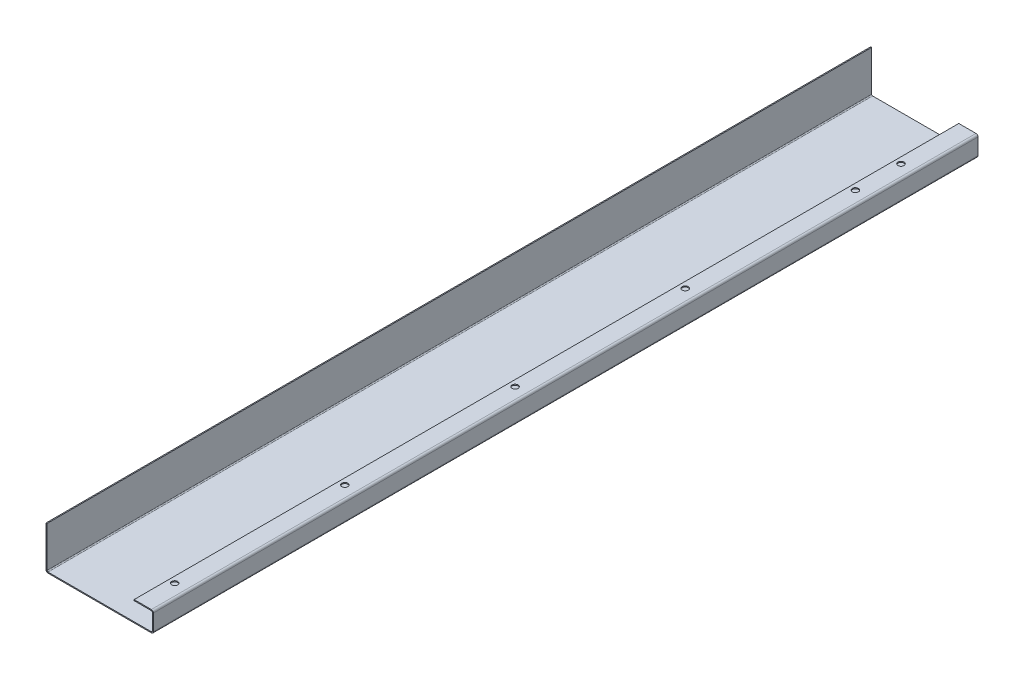
SolidWorks part; units mm, degrees
note: The reader was unsure of these and kept them because the rebuilt part matched: flange length of "Edge-Flange1", "Edge-Flange2", "Edge-Flange4".
ref_plane "Front Plane" through (0, 0, 0) normal (0, 0, 1) x (1, 0, 0)
ref_plane "Top Plane" through (0, 0, 0) normal (0, 1, 0) x (1, 0, 0)
ref_plane "Right Plane" through (0, 0, 0) normal (1, 0, 0) x (0, 0, -1)
sketch "Sketch1" plane through (0, 0, 0) normal (0, 1, 0) x (1, 0, 0)
  line L1 (0, 0) -> (106, 0)
  line L2 (0, 0) -> (0, 814)
  line L3 (0, 814) -> (106, 814)
  line L4 (106, 0) -> (106, 814)
  dimension "D1" = 106
  dimension "D2" = 814
base flange "Base-Flange1" sketch "Sketch1" thickness 1 reverse thickness direction no parameters "D1"=1
edge flange "Edge-Flange1" sketch "Sketch8" flange angle 90 flange length 19 flange position material inside bend radius 1 thickness 1 relief rectangular parameters "D6"=10
sketch "Sketch8" plane through (106, 0, 0) normal (1, 0, 0) x (0, 0, -1)
  line L0 (0, 0) -> (814, 0) construction
  line L1 (0, 0) -> (814, 0)
  line L2 (0, 0) -> (0, 19)
  line L3 (0, 19) -> (814, 19)
  line L4 (814, 19) -> (814, 0)
bend "EdgeBend1" bend radius 1 bend angle 90 parameters "D5"=1
edge flange "Edge-Flange2" sketch "Sketch11" flange angle 90 flange length 18 flange position material inside bend radius 1 thickness 1 relief rectangular parameters "D6"=10
sketch "Sketch11" plane through (105, 19, 0) normal (0, 1, 0) x (0, 0, -1)
  line L0 (814, 0) -> (0, 0) construction
  line L1 (814, 0) -> (0, 0)
  line L2 (0, 0) -> (0, 18)
  line L3 (0, 18) -> (814, 18)
  line L4 (814, 18) -> (814, 0)
bend "EdgeBend2" bend radius 1 bend angle 90 parameters "D5"=2
sketch "Sketch12" plane through (0, -1, 0) normal (0, -1, 0) x (-1, 0, 0)
  line L0 (0, 814) -> (-106, 752.8009)
  line L1 (-106, 814) -> (-106, 0) construction
  line L2 (-106, 752.8009) -> (-106, 814)
  line L3 (-106, 814) -> (0, 814)
  dimension "D1" = 30
extrude "Cut-Extrude1" [suppressed] cut sketch "Sketch12" against normal through all
edge flange "Edge-Flange3" [suppressed] sketch "Sketch15" flange angle 90 flange position material outside bend radius 1 thickness 1
sketch "Sketch15" plane through (433.0127, 0, -750) normal (0.5, 0, -0.866) x (-0.866, 0, -0.5)
  line L0 (414.5522, 0) -> (500, 0) construction
  line L1 (414.5522, 0) -> (500, 0)
  line L2 (414.5522, 0) -> (414.5522, 17.1875)
  line L3 (428.0522, 18.9875) -> (500, 18.9875)
  line L4 (500, 18.9875) -> (500, 0)
  line L5 (428.0522, 18.9875) -> (428.0522, 17.1875)
  line L6 (428.0522, 17.1875) -> (414.5522, 17.1875)
  dimension "D1" = 1.8
  dimension "D2" = 13.5
bend "EdgeBend3" bend radius 1 bend angle 90 parameters "D5"=3, "D6"=10, "D7"=18.9875
edge flange "Edge-Flange4" sketch "Sketch18" flange angle 90 flange length 41 flange position material inside bend radius 1 thickness 1 relief rectangular parameters "D6"=10
sketch "Sketch18" plane through (0, 0, 0) normal (-1, 0, 0) x (0, 0, 1)
  line L0 (-814, 0) -> (0, 0) construction
  line L1 (-814, 0) -> (0, 0)
  line L2 (-814, 0) -> (-814, 41)
  line L3 (-814, 41) -> (0, 41)
  line L4 (0, 41) -> (0, 0)
bend "EdgeBend4" bend radius 1 bend angle 90 parameters "D5"=3
sketch "Sketch19" plane through (0, 19, 0) normal (0, 1, 0) x (1, 0, 0)
  line L0 (104, 814) -> (87, 814) construction
  line L1 (87, 814) -> (87, 0) construction
  circle A0 centre (93, 751) radius 3
  circle A7 centre (93, 706) radius 3
  circle A8 centre (93, 538) radius 3
  circle A9 centre (93, 370) radius 3
  circle A10 centre (93, 202) radius 3
  circle A11 centre (93, 34) radius 3
  dimension "D1" = 6
  dimension "D3" = 6
  dimension "D5" = 5
  dimension "D4" = 45
  dimension "D2" = 63
extrude "Cut-Extrude2" cut sketch "Sketch19" against normal blind 10 normal cut yes
sketch "Bend-Lines1" [suppressed] plane through (0, 0, 0) normal (0, 1, 0) x (1, 0, 0)
sketch "Bounding-Box1" [suppressed] plane through (0, 0, 0) normal (0, 1, 0) x (1, 0, 0)
sheet metal parameters "Sheet-Metal1" thickness 1 parameters "D1"=1
flat pattern "Flat-Pattern1" [suppressed]
sketch "Bend-Lines2" plane through (0, 0, 0) normal (0, 1, 0) x (1, 0, 0)
sketch3d "Bounding-Box2" [suppressed]
  line L0 (0, 0, 0) -> (0, 1577, 0) construction
  line L1 (-76, 0, 0) -> (-76, 1577, 0) construction
  line L2 (0, 0, 0) -> (-76, 0, 0) construction
  line L3 (0, 1577, 0) -> (-76, 1577, 0) construction
sheet metal parameters "Sheet-Metal2" thickness 1 parameters "D1"=1
flat pattern "Flat-Pattern1"
sketch "Bend-Lines2" plane through (0, 0, 0) normal (0, 1, 0) x (1, 0, 0)
  line L0 (75.1781, 0) -> (75.1781, 1577) construction
  line L1 (75.1781, 0) -> (75.1781, 1577) construction
sketch3d "Bounding-Box2" [suppressed]
  line L0 (0, 0, 0) -> (0, 1577, 0) construction
  line L1 (95.3562, 0, 0) -> (95.3562, 1577, 0) construction
  line L2 (0, 0, 0) -> (95.3562, 0, 0) construction
  line L3 (0, 1577, 0) -> (95.3562, 1577, 0) construction
bend of the flat pattern "Flatten-<EdgeBend1>1"
sheet metal parameters "Sheet-Metal3" thickness 1 parameters "D1"=1
flat pattern "Flat-Pattern1"
sketch "Bend-Lines2" plane through (0, 0, 0) normal (0, 1, 0) x (1, 0, 0)
  line L0 (75.1781, 0) -> (75.1781, 1000) construction
  line L1 (75.1781, 0) -> (75.1781, 1000) construction
  line L2 (93.5343, 0) -> (93.5343, 1000) construction
  line L3 (93.5343, 0) -> (93.5343, 1000) construction
sketch3d "Bounding-Box2" [suppressed]
  line L0 (0, 0, 0) -> (0, 1000, 0) construction
  line L1 (105.7124, 0, 0) -> (105.7124, 1000, 0) construction
  line L2 (0, 0, 0) -> (105.7124, 0, 0) construction
  line L3 (0, 1000, 0) -> (105.7124, 1000, 0) construction
bend of the flat pattern "Flatten-<EdgeBend1>1"
bend of the flat pattern "Flatten-<EdgeBend2>1"
sheet metal parameters "Sheet-Metal4" thickness 1 parameters "D1"=1
flat pattern "Flat-Pattern1"
sketch "Bend-Lines2" plane through (0, 0, 0) normal (0, 1, 0) x (1, 0, 0)
  line L0 (75.1781, 0) -> (75.1781, 956.6987) construction
  line L1 (75.1781, 0) -> (75.1781, 956.6987) construction
  line L2 (93.5343, 0) -> (93.5343, 956.6987) construction
  line L3 (93.5343, 0) -> (93.5343, 956.6987) construction
sketch3d "Bounding-Box2" [suppressed]
  line L0 (0, 0, 0) -> (0, 1000, 0) construction
  line L1 (105.7124, 0, 0) -> (105.7124, 1000, 0) construction
  line L2 (0, 0, 0) -> (105.7124, 0, 0) construction
  line L3 (0, 1000, 0) -> (105.7124, 1000, 0) construction
bend of the flat pattern "Flatten-<EdgeBend1>1"
bend of the flat pattern "Flatten-<EdgeBend2>1"
sheet metal parameters "Sheet-Metal5" thickness 1 parameters "D1"=1
flat pattern "Flat-Pattern1"
sketch "Bend-Lines2" plane through (0, 0, 0) normal (0, 1, 0) x (1, 0, 0)
  line L0 (75.1781, 0) -> (75.1781, 956.6987) construction
  line L1 (75.1781, 0) -> (75.1781, 956.6987) construction
  line L2 (93.5343, 0) -> (93.5343, 956.6987) construction
  line L3 (93.5343, 0) -> (93.5343, 956.6987) construction
  line L4 (74.089, 957.4303) -> (0.339, 1000.0099) construction
  line L5 (74.089, 957.4303) -> (0.339, 1000.0099) construction
sketch3d "Bounding-Box2" [suppressed]
  line L0 (0, 0, 0) -> (0, 1016.7521, 0) construction
  line L1 (105.7124, 0, 0) -> (105.7124, 1016.7521, 0) construction
  line L2 (0, 0, 0) -> (105.7124, 0, 0) construction
  line L3 (0, 1016.7521, 0) -> (105.7124, 1016.7521, 0) construction
bend of the flat pattern "Flatten-<EdgeBend1>1"
bend of the flat pattern "Flatten-<EdgeBend2>1"
bend of the flat pattern "Flatten-<EdgeBend3>1"
sheet metal parameters "Sheet-Metal6" thickness 1 parameters "D1"=1
flat pattern "Flat-Pattern1"
sketch "Bend-Lines2" plane through (0, 0, 0) normal (0, 1, 0) x (1, 0, 0)
  line L0 (91.1781, 0) -> (91.1781, 875) construction
  line L1 (91.1781, 0) -> (91.1781, 875) construction
  line L2 (109.5343, 0) -> (109.5343, 875) construction
  line L3 (109.5343, 0) -> (109.5343, 875) construction
  line L4 (0.8219, 875) -> (0.8219, 0) construction
  line L5 (0.8219, 875) -> (0.8219, 0) construction
sketch3d "Bounding-Box2" [suppressed]
  line L0 (-40.3562, 0, 0) -> (-40.3562, 875, 0) construction
  line L1 (121.7124, 0, 0) -> (121.7124, 875, 0) construction
  line L2 (-40.3562, 0, 0) -> (121.7124, 0, 0) construction
  line L3 (-40.3562, 875, 0) -> (121.7124, 875, 0) construction
bend of the flat pattern "Flatten-<EdgeBend1>1"
bend of the flat pattern "Flatten-<EdgeBend2>1"
bend of the flat pattern "Flatten-<EdgeBend4>1"
sheet metal parameters "Sheet-Metal7" thickness 1 parameters "D1"=1
flat pattern "Flat-Pattern1"
sketch "Bend-Lines2" plane through (0, 0, 0) normal (0, 1, 0) x (1, 0, 0)
  line L0 (105.1781, 0) -> (105.1781, 814) construction
  line L1 (105.1781, 0) -> (105.1781, 814) construction
  line L2 (123.5343, 0) -> (123.5343, 814) construction
  line L3 (123.5343, 0) -> (123.5343, 814) construction
  line L4 (0.8219, 814) -> (0.8219, 0) construction
  line L5 (0.8219, 814) -> (0.8219, 0) construction
sketch3d "Bounding-Box2" [suppressed]
  line L0 (-40.3562, 0, 0) -> (-40.3562, 814, 0) construction
  line L1 (141.7124, 0, 0) -> (141.7124, 814, 0) construction
  line L2 (-40.3562, 0, 0) -> (141.7124, 0, 0) construction
  line L3 (-40.3562, 814, 0) -> (141.7124, 814, 0) construction
bend of the flat pattern "Flatten-<EdgeBend1>1"
bend of the flat pattern "Flatten-<EdgeBend2>1"
bend of the flat pattern "Flatten-<EdgeBend4>1"
